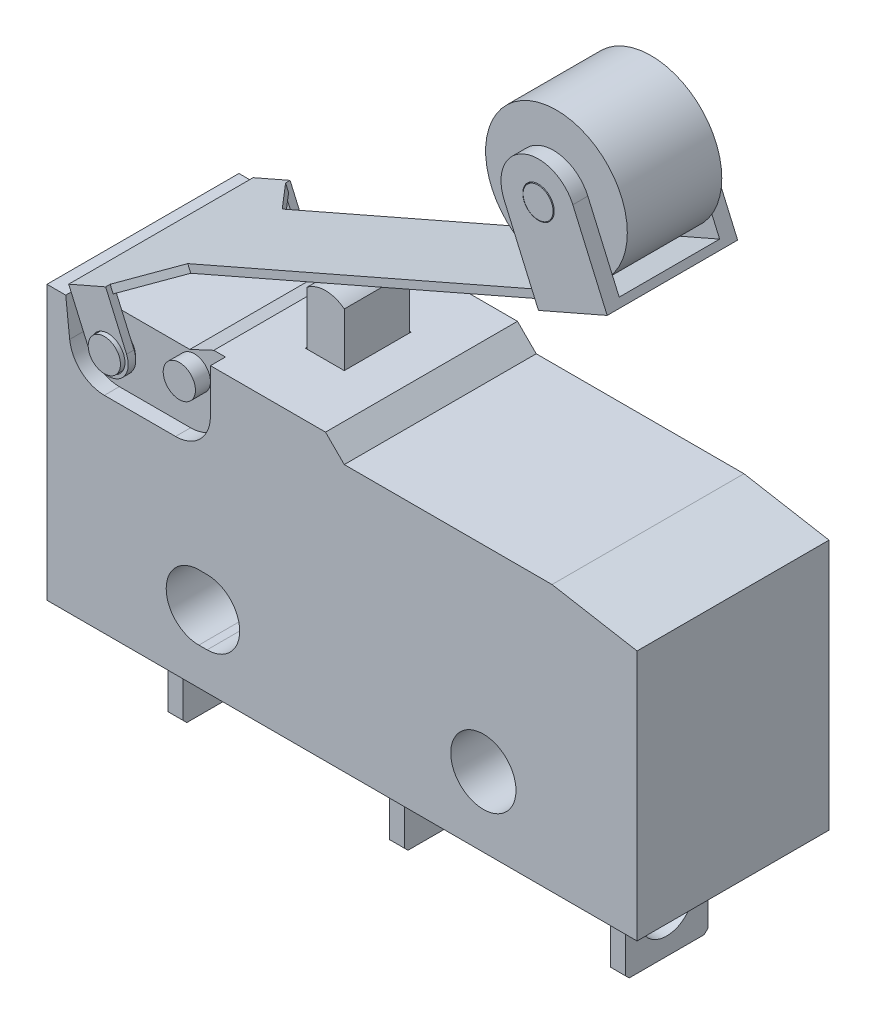
SolidWorks part; units mm, degrees
ref_plane "Front" through (0, 0, 0) normal (0, 0, 1) x (1, 0, 0)
ref_plane "Top" through (0, 0, 0) normal (0, 1, 0) x (1, 0, 0)
ref_plane "Right" through (0, 0, 0) normal (1, 0, 0) x (0, 0, -1)
sketch "Sketch2" plane through (0, 0, 0) normal (0, 0, 1) x (1, 0, 0)
  line L0 (-4.8514, 3.4671) -> (-4.572, 3.4671)
  line L1 (9.9949, 8.509) -> (7.1139, 9.017)
  line L2 (-9.9949, 9.271) -> (-9.9949, 0)
  line L3 (-9.9949, 0) -> (9.9949, 0)
  line L4 (9.9949, 8.509) -> (9.9949, 0)
  line L5 (-4.8514, 1.2573) -> (-4.572, 1.2573)
  line L6 (-4.7117, 3.4671) -> (-4.7117, 1.2573) construction
  line L7 (4.7879, 2.3622) -> (-4.572, 2.3622) construction
  line L8 (7.1139, 9.017) -> (0.0762, 9.017)
  line L9 (0.0762, 9.017) -> (-0.5588, 9.652)
  line L10 (-0.5588, 9.652) -> (-4.8514, 9.652)
  line L11 (-4.8514, 9.652) -> (-5.6646, 9.271)
  line L12 (-5.6646, 9.271) -> (-9.9949, 9.271)
  line L13 (-2.7051, 9.652) -> (-2.7051, 2.3622) construction
  line L14 (-4.8514, 9.652) -> (-4.8514, 3.4671) construction
  circle A0 centre (4.7879, 2.3622) radius 1.1049
  arc A1 (-4.8514, 3.4671) -> (-4.8514, 1.2573) centre (-4.8514, 2.3622) ccw
  arc A2 (-4.572, 1.2573) -> (-4.572, 3.4671) centre (-4.572, 2.3622) ccw
  dimension "D4" = 5.207
  dimension "D5" = 2.2098
  dimension "D6" = 2.4892
  dimension "D7" = 6.6548
  dimension "D8" = 7.2898
  dimension "D9" = 7.493
  dimension "D13" = 6.9088
  dimension "D1" = 19.9898
  dimension "D2" = 2.3622
  dimension "D3" = 9.4996
  dimension "D10" = 0.508
  dimension "D11" = 10
  dimension "D12" = 135
extrude "Extrude1" add sketch "Sketch2" along normal mid plane 6.5024
sketch "Sketch3" plane through (0, 0, 0) normal (0, 0, 1) x (1, 0, 0)
  line L0 (-3.3401, 9.271) -> (-3.3401, 11.4357)
  line L1 (-2.7051, 9.271) -> (-2.7051, 10.6426) construction
  line L2 (-2.0701, 11.4357) -> (-2.0701, 9.271)
  line L3 (-2.0701, 9.271) -> (-3.3401, 9.271)
  line L4 (-3.3401, 11.4357) -> (-2.0701, 11.4357) construction
  line L5 (-2.7051, 9.652) -> (-2.7051, 2.3622) construction
  line L6 (-5.6646, 9.271) -> (-9.9949, 9.271) construction
  arc A0 (-3.3401, 11.4357) -> (-2.0701, 11.4357) centre (-2.7051, 10.6426) cw
  arc A1 (-4.8514, 3.4671) -> (-4.8514, 1.2573) centre (-4.8514, 2.3622) ccw construction
  dimension "D1" = 9.2964
  dimension "D3" = 1.016
  dimension "D2" = 1.27
extrude "Extrude2" add sketch "Sketch3" along normal mid plane 2.2098 separate body
sketch "Sketch4" plane through (0, 9.652, 0) normal (0, 1, 0) x (-1, 0, 0)
  line L0 (2.0701, -1.1049) -> (3.3401, -1.1049) construction
  line L1 (3.3401, 1.1049) -> (3.3401, -1.1049) construction
  line L2 (2.0701, 1.1049) -> (2.0701, -1.1049) construction
  line L3 (3.3401, 1.1049) -> (2.0701, 1.1049) construction
  line L4 (2.0701, -1.1049) -> (3.3401, -1.1049) construction
  line L5 (3.3401, 1.1049) -> (3.3401, -1.1049) construction
  line L6 (2.0701, 1.1049) -> (2.0701, -1.1049) construction
  line L7 (3.3401, 1.1049) -> (2.0701, 1.1049) construction
  line L8 (3.3655, 1.1303) -> (3.3655, -1.1303)
  line L9 (2.0447, -1.1303) -> (3.3655, -1.1303)
  line L10 (2.0447, 1.1303) -> (2.0447, -1.1303)
  line L11 (3.3655, 1.1303) -> (2.0447, 1.1303)
  dimension "D1" = 0.0254
extrude "Cut-Extrude1" cut sketch "Sketch4" against normal blind 1.016
sketch "Sketch5" plane through (0, 0, 3.2512) normal (0, 0, 1) x (1, 0, 0)
  line L0 (-9.2329, 9.271) -> (-9.2329, 8.1661) construction
  line L1 (-8.0518, 6.985) -> (-5.6388, 6.985)
  line L2 (-4.4577, 8.1661) -> (-4.4577, 9.652)
  line L3 (-5.6646, 9.271) -> (-9.9949, 9.271) construction
  line L4 (-4.8514, 9.652) -> (-5.6646, 9.271) construction
  line L5 (-0.5588, 9.652) -> (-4.8514, 9.652) construction
  line L6 (-5.6646, 9.271) -> (-9.2329, 9.271)
  line L7 (-4.8514, 9.652) -> (-5.6646, 9.271)
  line L8 (-4.4577, 9.652) -> (-4.8514, 9.652)
  line L9 (-9.9949, 9.271) -> (-9.9949, 0) construction
  line L10 (-9.226, 8.0385) -> (-9.3599, 9.271)
  line L11 (-5.6646, 9.271) -> (-9.9949, 9.271) construction
  line L12 (-9.3599, 9.271) -> (-9.2329, 9.271)
  circle A0 centre (-5.5118, 8.6741) radius 0.5461
  circle A1 centre (-8.0518, 8.1661) radius 0.5461
  arc A2 (-9.226, 8.0385) -> (-8.0518, 6.985) centre (-8.0518, 8.1661) ccw
  arc A3 (-5.6388, 6.985) -> (-4.4577, 8.1661) centre (-5.6388, 8.1661) ccw
  dimension "D4" = 0.0508
  dimension "D5" = 1.0922
  dimension "D6" = 2.54
  dimension "D7" = 0.508
  dimension "D1" = 0.762
  dimension "D2" = 0.508
  dimension "D3" = 0.635
  dimension "D8" = 0.127
extrude "Cut-Extrude2" cut sketch "Sketch5" against normal blind 0.508
mirror "Mirror1" about plane through (0, 0, 0) normal (0, 0, 1) of "Cut-Extrude2"
ref_plane "Plane1" through (-7.493, 0, 0) normal (1, 0, 0) x (0, 0, -1)
sketch "Sketch10" plane through (-7.493, 0, 0) normal (1, 0, 0) x (0, 0, -1)
  line L0 (-1.397, 0) -> (-1.397, -3.0734)
  line L1 (-1.27, -3.2004) -> (1.27, -3.2004)
  line L2 (1.397, -3.0734) -> (1.397, 0)
  line L3 (1.397, 0) -> (-1.397, 0)
  line L4 (0, -3.2004) -> (0, -1.7018) construction
  line L5 (0, 0) -> (0, -1.7018) construction
  line L6 (-1.397, -3.0734) -> (-1.27, -3.2004)
  line L7 (1.27, -3.2004) -> (1.397, -3.0734)
  circle A0 centre (0, -1.7018) radius 0.9017
  point P1 (-1.397, -3.2004)
  point P3 (1.397, -3.2004)
  dimension "D2" = 1.8034
  dimension "D1" = 3.2004
  dimension "D3" = 2.794
  dimension "D4" = 1.4986
  dimension "D5" = 0.127
  dimension "D6" = 45
  dimension "D7" = 0.127
  dimension "D8" = 45
extrude "Extrude6" add sketch "Sketch10" along normal mid plane 0.508
pattern_linear "LPattern1" count 3 spacing 7.493 along (1, 0, 0) of "Extrude6"
sketch "Sketch6" plane through (0, 0, 0) normal (0, 0, 1) x (1, 0, 0)
  line L0 (-9.2846, 9.2829) -> (7.941, 16.804)
  line L1 (7.941, 16.804) -> (7.8394, 17.0367)
  line L2 (7.8394, 17.0367) -> (-9.3863, 9.5157)
  line L3 (-9.3863, 9.5157) -> (-9.2846, 9.2829)
  line L6 (5.5116, 16.0204) -> (4.4495, 18.4529) construction
  line L7 (6.7773, 19.4693) -> (7.8394, 17.0367) construction
  line L10 (-9.2846, 9.2829) -> (-8.6777, 7.8928) construction
  line L11 (-7.4259, 8.4394) -> (-8.0328, 9.8295) construction
  circle A0 centre (-8.0518, 8.1661) radius 0.5461 construction
  circle A2 centre (5.6134, 18.9611) radius 2.4003 construction
  arc A6 (-8.6777, 7.8928) -> (-7.4259, 8.4394) centre (-8.0518, 8.1661) ccw construction
  circle A7 centre (4.7879, 2.3622) radius 1.1049 construction
  arc A8 (4.4495, 18.4529) -> (6.7773, 19.4693) centre (5.6134, 18.9611) cw construction
  dimension "D1" = 4.8006
  dimension "D2" = 18.9992
  dimension "D3" = 0.0762
  dimension "D6" = 2.54
  dimension "D4" = 0.8255
  dimension "D5" = 0.254
  dimension "D7" = 0.254
  dimension "D8" = 17.526
extrude "Extrude3" add sketch "Sketch6" along normal mid plane 3.2004 separate body
sketch "Sketch8" plane through (0, 0, 3.2512) normal (0, 0, 1) x (1, 0, 0)
  line L0 (-7.4259, 8.4394) -> (-8.0328, 9.8295) construction
  line L1 (-9.2846, 9.2829) -> (-8.6777, 7.8928) construction
  line L2 (-7.4259, 8.4394) -> (-8.1345, 10.0622)
  line L3 (-9.3863, 9.5157) -> (-8.6777, 7.8928)
  line L4 (7.8394, 17.0367) -> (-9.3863, 9.5157) construction
  line L5 (-8.1345, 10.0622) -> (-9.3863, 9.5157)
  arc A1 (-8.6777, 7.8928) -> (-7.4259, 8.4394) centre (-8.0518, 8.1661) ccw construction
  arc A3 (-8.6777, 7.8928) -> (-7.4259, 8.4394) centre (-8.0518, 8.1661) ccw
  circle A5 centre (-8.0518, 8.1661) radius 0.5715
  circle A6 centre (-8.0518, 8.1661) radius 0.5715
  dimension "D1" = 0.0254
extrude "Extrude4" add sketch "Sketch8" against normal blind 0.254 from offset 0.127 separate body offset against normal yes
sketch "Sketch9" plane through (0, 0, 1.6002) normal (0, 0, 1) x (1, 0, 0)
  line L0 (-7.4259, 8.4394) -> (-8.0328, 9.8295) construction
  line L1 (-9.3863, 9.5157) -> (-9.2846, 9.2829) construction
  line L2 (-9.2846, 9.2829) -> (7.941, 16.804) construction
  line L3 (7.8394, 17.0367) -> (-9.3863, 9.5157) construction
  line L4 (-8.0328, 9.8295) -> (-8.1345, 10.0622)
  line L5 (-9.3863, 9.5157) -> (-9.2846, 9.2829)
  line L6 (-9.2846, 9.2829) -> (-8.0328, 9.8295)
  line L7 (-8.1345, 10.0622) -> (-9.3863, 9.5157)
extrude "Extrude5" add sketch "Sketch9" along normal up to surface (1.27 mm away) up to face at (-7.4803, 8.1661, 2.8702)
mirror "Mirror7" about plane through (0, 0, 0) normal (0, 0, 1) of bodies 116
combine bodies "Combine1" operation type add bodies to combine 118 114 116
sketch "Sketch11" plane through (0, 0, 0) normal (0, 0, 1) x (1, 0, 0)
  circle A0 centre (5.6134, 18.9611) radius 2.4003 construction
  circle A1 centre (5.6134, 18.9611) radius 2.4003
extrude "Extrude7" add sketch "Sketch11" along normal mid plane 3.2004
sketch "Sketch12" plane through (0, 0, 0) normal (0, 0, 1) x (1, 0, 0)
  circle A0 centre (5.6134, 18.9611) radius 0.508
  dimension "D1" = 1.016
extrude "Extrude8" add sketch "Sketch12" along normal mid plane 4.445
sketch "Sketch13" plane through (0, 0, 1.6002) normal (0, 0, 1) x (1, 0, 0)
  line L0 (-9.2846, 9.2829) -> (7.941, 16.804) construction
  line L1 (6.7773, 19.4693) -> (7.8394, 17.0367) construction
  line L2 (5.5116, 16.0204) -> (4.4495, 18.4529) construction
  line L3 (5.6132, 15.7876) -> (7.941, 16.804)
  line L4 (6.7773, 19.4693) -> (7.941, 16.804)
  line L5 (5.6132, 15.7876) -> (4.4495, 18.4529)
  line L6 (5.6134, 18.9611) -> (5.6134, 19.4691) construction
  line L7 (5.6134, 19.4691) -> (5.6134, 19.4945) construction
  circle A0 centre (5.6134, 18.9611) radius 0.508 construction
  arc A1 (6.7773, 19.4693) -> (4.4495, 18.4529) centre (5.6134, 18.9611) ccw construction
  circle A2 centre (5.6134, 18.9611) radius 0.508 construction
  arc A3 (6.7773, 19.4693) -> (4.4495, 18.4529) centre (5.6134, 18.9611) ccw
  circle A4 centre (5.6134, 18.9611) radius 0.5334
  dimension "D1" = 0.0254
extrude "Extrude9" add sketch "Sketch13" along normal blind 0.508 from offset 0.1016 separate body
mirror "Mirror8" about plane through (0, 0, 0) normal (0, 0, 1) of bodies 124
sketch "Sketch14" plane through (0, 0, 0) normal (0, 0, 1) x (1, 0, 0)
  line L0 (5.5116, 16.0204) -> (4.4495, 18.4529) construction
  line L1 (7.941, 16.804) -> (7.8394, 17.0367) construction
  line L2 (-9.2846, 9.2829) -> (7.941, 16.804) construction
  line L3 (7.8394, 17.0367) -> (-9.3863, 9.5157) construction
  line L4 (5.6132, 15.7876) -> (5.5116, 16.0204)
  line L5 (7.941, 16.804) -> (7.8394, 17.0367)
  line L6 (5.6132, 15.7876) -> (7.941, 16.804)
  line L7 (7.8394, 17.0367) -> (5.5116, 16.0204)
extrude "Extrude10" add sketch "Sketch14" along normal up to vertex (2.2098 mm away) and the other way up to vertex (2.2098 mm away) up to point (7.941, 16.804, 2.2098) other way up to point (7.941, 16.804, -2.2098)
sketch "Sketch15" plane through (0, 0, 0) normal (0, 0, 1) x (1, 0, 0)
  line L0 (9.3628, 8.1661) -> (9.3628, 20.7376) construction
  line L1 (9.3628, 20.7376) -> (3.9992, 20.7376) construction
  line L2 (-8.0518, 8.1661) -> (3.9992, 20.7376) construction
  line L3 (-8.0518, 8.1661) -> (6.9925, 16.9376) construction
  line L4 (6.9925, 16.9376) -> (9.3628, 16.9376) construction
  line L5 (-8.0518, 8.1661) -> (7.3794, 16.2376) construction
  line L6 (7.3794, 16.2376) -> (9.3628, 16.2376) construction
  line L7 (-8.0518, 8.1661) -> (8.0754, 14.7376) construction
  line L8 (8.0754, 14.7376) -> (9.3628, 14.7376) construction
  circle A1 centre (5.6134, 18.9611) radius 2.4003
  circle A5 centre (8.0557, 14.7856) radius 2.4003 construction
  circle A8 centre (8.3427, 14.0391) radius 2.4003 construction
  circle A9 centre (8.8258, 12.4576) radius 2.4003 construction
  arc A10 (9.3628, 8.1661) -> (3.9992, 20.7376) centre (-8.0518, 8.1661) ccw construction
  circle A11 centre (5.6134, 18.9611) radius 2.4003 construction
  point P10 (3.9992, 20.7376)
  point P27 (-8.0518, 8.1661)
  dimension "D1" = 4.5
  dimension "D2" = 0.7
  dimension "D3" = 1.5
sketch "Sketch16" plane through (0, 0, 0) normal (0, 0, 1) x (1, 0, 0)
  circle A0 centre (8.8258, 12.4576) radius 2.4003 construction
  circle A1 centre (8.0557, 14.7856) radius 2.4003 construction
  circle A2 centre (8.3427, 14.0391) radius 2.4003 construction
  circle A3 centre (8.8258, 12.4576) radius 2.4003 construction
  circle A4 centre (8.0557, 14.7856) radius 2.4003 construction
  circle A5 centre (8.3427, 14.0391) radius 2.4003 construction
  point P9 (8.0754, 14.7376)
  point P10 (7.3794, 16.2376)
  point P12 (6.9925, 16.9376)
  point P14 (3.9992, 20.7376)
chamfer "Chamfer1" distance 1.3716 angle 45 2 edges
